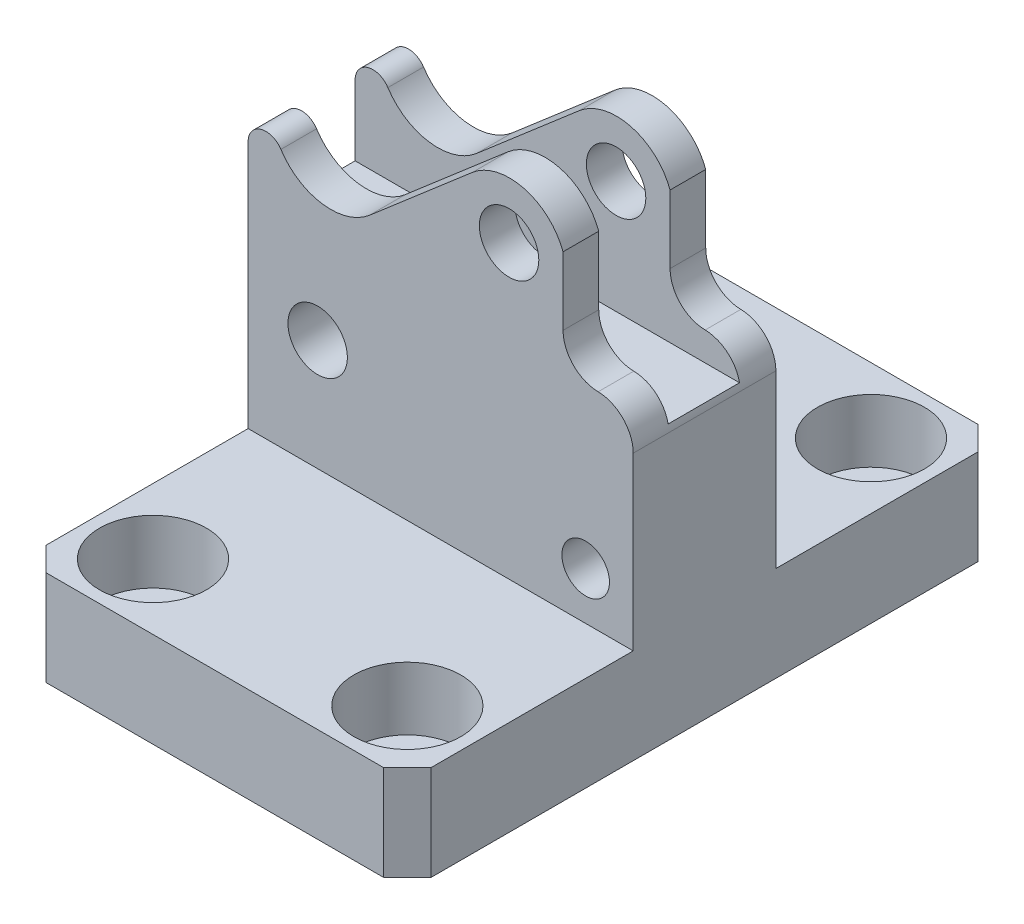
SolidWorks part; units mm, degrees
ref_plane "前基準面" through (0, 0, 0) normal (0, 0, 1) x (1, 0, 0)
ref_plane "上基準面" through (0, 0, 0) normal (0, 1, 0) x (1, 0, 0)
ref_plane "右基準面" through (0, 0, 0) normal (1, 0, 0) x (0, 0, -1)
sketch "草圖1" plane through (0, 0, 0) normal (1, 0, 0) x (0, 0, -1)
  line L0 (-19.9, 18) -> (-19.9, 3) construction
  line L6 (-13.9, 3) -> (-25.9, 3)
  line L7 (-13.9, 3) -> (-13.9, 38)
  line L8 (-13.9, 38) -> (-16.9, 38)
  line L9 (-16.9, 38) -> (-16.9, 18)
  line L10 (-16.9, 18) -> (-22.9, 18)
  line L11 (-22.9, 18) -> (-22.9, 38)
  line L12 (-22.9, 38) -> (-25.9, 38)
  line L13 (-25.9, 38) -> (-25.9, 3)
  dimension "D1" = 35
  dimension "D2" = 6
  dimension "D3" = 12
  dimension "D4" = 20
extrude "填料-伸長1" add sketch "草圖1" against normal blind 35
sketch "草圖2" plane through (0, 0, 13.9) normal (0, 0, 1) x (1, 0, 0)
  line L0 (-54.8077, 56.2225) -> (-54.8077, -32.4384)
  line L1 (-54.8077, -32.4384) -> (27.661, -32.4384)
  line L2 (27.661, -32.4384) -> (27.661, 56.2225)
  line L3 (27.661, 56.2225) -> (-54.8077, 56.2225)
  line L4 (-32.391, 23.8178) -> (-32.391, 3)
  line L5 (-32.391, 3) -> (0, 3)
  line L6 (-35, 3) -> (0, 3) construction
  line L9 (0, 3) -> (0, 20.4)
  line L10 (0, 20.4) -> (-2.9, 20.4)
  line L11 (-5.9, 23.4) -> (-5.9, 29.1213)
  line L12 (-13.5314, 31.0889) -> (-22.1788, 23.6454)
  arc A0 (-29.6348, 24.7129) -> (-32.391, 23.8178) centre (-30.8931, 23.8963) ccw
  arc A4 (-2.9, 20.4) -> (-5.9, 23.4) centre (-2.9, 23.4) cw
  arc A5 (-5.9, 29.1213) -> (-13.5314, 31.0889) centre (-10.4, 27.451) ccw
  arc A6 (-22.1788, 23.6454) -> (-29.6348, 24.7129) centre (-25.4407, 27.4349) cw
extrude "除料-伸長1" cut sketch "草圖2" along normal blind 40
sketch "草圖10" plane through (0, 0, 25.9) normal (0, 0, 1) x (1, 0, 0)
  line L2 (-25.4407, 27.4349) -> (-10.4407, 27.5) construction
  line L3 (-32.391, 3) -> (0, 3) construction
  circle A0 centre (-10.4407, 27.5) radius 2.5
  dimension "D1" = 5
  dimension "D2" = 24.5
  dimension "D3" = 15
extrude "除料-伸長6" cut sketch "草圖10" against normal through all
sketch "草圖11" plane through (0, 0, 25.9) normal (0, 0, 1) x (1, 0, 0)
  circle A0 centre (-26.5407, 12.35) radius 2.5
  circle A1 centre (-10.4407, 27.5) radius 2.5 construction
  dimension "D1" = 5
  dimension "D3" = 15.15
  dimension "D2" = 16.1
extrude "除料-伸長7" cut sketch "草圖11" against normal through all
sketch "草圖13" plane through (0, 0, 25.9) normal (0, 0, 1) x (1, 0, 0)
  line L0 (-32.391, 3) -> (0, 3) construction
  line L1 (0, 20.4) -> (0, 3) construction
  circle A0 centre (-4, 7) radius 2
  dimension "D1" = 4
  dimension "D2" = 4
  dimension "D3" = 4
extrude "除料-伸長8" cut sketch "草圖13" against normal through all
fillet "圓角1" radius 3 1 edges at (0, 20.4, 15.4)
sketch "草圖14" plane through (0, 3, 0) normal (0, -1, 0) x (1, 0, 0)
  line L0 (0, 19.9) -> (-32.391, 19.9) construction
  line L1 (-32.391, 44.9) -> (0, 44.9)
  line L2 (-32.391, 44.9) -> (-32.391, -5.1)
  line L3 (-32.391, -5.1) -> (0, -5.1)
  line L4 (0, 44.9) -> (0, -5.1)
  line L5 (0, 25.9) -> (0, 13.9) construction
  line L6 (-32.391, 25.9) -> (-32.391, 13.9) construction
  dimension "D1" = 50
extrude "填料-伸長2" add sketch "草圖14" along normal blind 8
chamfer "導角1" distance 2 angle 45 4 edges at (-32.391, -1, -5.1) (0, -1, -5.1) (-32.391, -1, 44.9) (0, -1, 44.9)
hole_wizard "M5 內六角圓柱頭螺釘的柱孔1" positions "草圖16" profile "草圖15" counterbore size "M5" standard "Gb" end condition through all
sketch "草圖16" plane through (0, 3, 0) normal (0, 1, 0) x (1, 0, 0)
  line L1 (-26.891, -0.4) -> (-5.5, -0.4) construction
  line L2 (-26.891, -0.4) -> (-26.891, -39.4) construction
  line L3 (-26.891, -39.4) -> (-5.5, -39.4) construction
  line L4 (-5.5, -0.4) -> (-5.5, -39.4) construction
  line L5 (-30.391, 5.1) -> (-2, 5.1) construction
  line L6 (0, -25.9) -> (0, -42.9) construction
  line L7 (-32.391, -42.9) -> (-32.391, -25.9) construction
  line L8 (-2, -44.9) -> (-30.391, -44.9) construction
  point P0 (-26.891, -0.4)
  point P2 (-5.5, -0.4)
  point P4 (-5.5, -39.4)
  point P6 (-26.891, -39.4)
  dimension "D1" = 5.5
  dimension "D2" = 5.5
  dimension "D3" = 5.5
  dimension "D4" = 5.5
sketch "草圖15" plane through (-26.891, 3, 0.4) normal (1, 0, 0) x (0, 0, 1)
  line L0 (0, 0) -> (0, 8)
  line L1 (0, 8) -> (2.75, 8)
  line L3 (2.75, 8) -> (2.75, 5.3)
  line L4 (2.75, 5.3) -> (4.5, 5.3)
  line L5 (4.5, 5.3) -> (4.5, 0)
  line L7 (4.5, 0) -> (0, 0)
  line L11 (0, -6.35) -> (0, 107.95) construction
  dimension "貫穿孔直徑" = 5.5
  dimension "貫穿孔深度" = 8
  dimension "柱孔直徑" = 9
  dimension "柱孔深度" = 5.3
